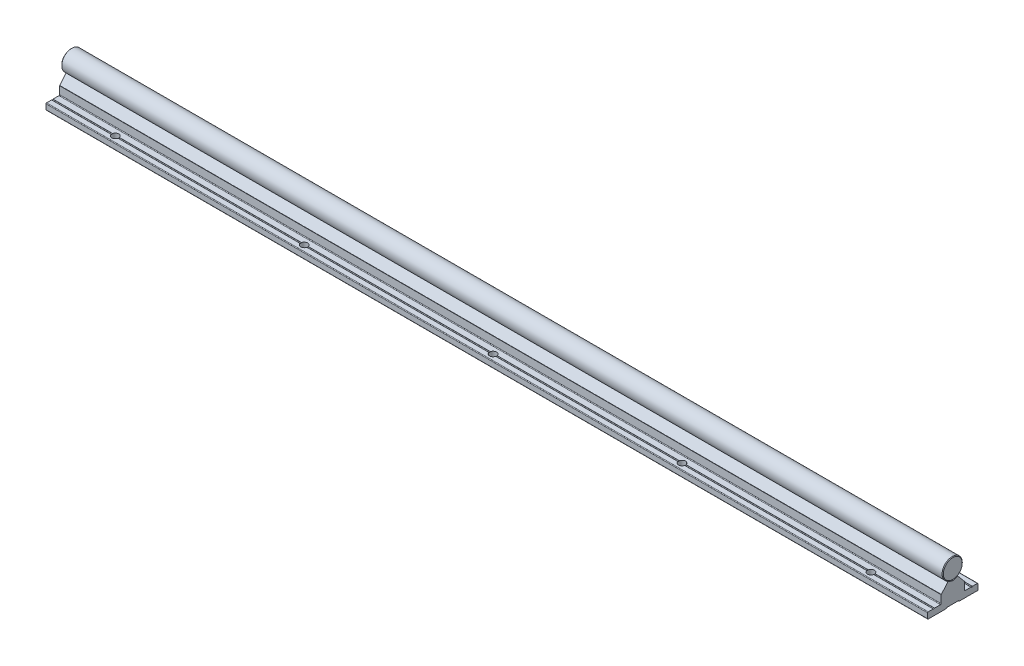
SolidWorks part; units mm, degrees
note: The reader was unsure of these and kept them because the rebuilt part matched: shared geometry of "Эскиз1<3>".
ref_plane "Спереди" through (0, 0, 0) normal (0, 0, 1) x (1, 0, 0)
ref_plane "Сверху" through (0, 0, 0) normal (0, 1, 0) x (1, 0, 0)
ref_plane "Справа" through (0, 0, 0) normal (1, 0, 0) x (0, 0, -1)
sketch "Эскиз1" plane through (0, 0, 0) normal (1, 0, 0) x (0, 0, -1)
  line L0 (0, 0) -> (0, -25) construction
  line L1 (0, -25) -> (-20, -25) construction
  line L2 (-4.75, -25) -> (-20, -25)
  line L3 (-20, -25) -> (-20, -20)
  line L4 (-20, -20) -> (-9.25, -20)
  line L5 (-9.25, -20) -> (-9.25, -13.3)
  line L6 (-9.25, -13.3) -> (-9.1101, -13.3)
  line L7 (-9.1101, -13.3) -> (-4, -7.21)
  line L8 (-4, -7.21) -> (-3.8, -7.21)
  line L9 (-3.8, -7.21) -> (0, -8.3557)
  line L10 (-2.75, -7.5266) -> (-2.75, -19) construction
  line L11 (-2.75, -19) -> (-4.75, -19) construction
  line L12 (-4.75, -19) -> (-4.75, -25) construction
  line L13 (-4.75, -25) -> (-4.75, -24.4)
  line L14 (-4.75, -24.4) -> (4.75, -24.4)
  line L15 (4.75, -25) -> (4.75, -24.4)
  line L16 (4.75, -25) -> (20, -25)
  line L17 (20, -25) -> (20, -20)
  line L18 (20, -20) -> (9.25, -20)
  line L19 (9.25, -20) -> (9.25, -13.3)
  line L20 (9.25, -13.3) -> (9.1101, -13.3)
  line L21 (9.1101, -13.3) -> (4, -7.21)
  line L22 (4, -7.21) -> (3.8, -7.21)
  line L23 (3.8, -7.21) -> (0, -8.3557)
  line L24 (-15, -20) -> (-15, -25) construction
  line L25 (-15.5, -20) -> (-15, -20.5)
  line L26 (-15, -20.5) -> (-14.5, -20)
  line L27 (15.5, -20) -> (15, -20.5)
  line L28 (15, -20) -> (15, -25) construction
  line L29 (15, -20.5) -> (14.5, -20)
  circle A0 centre (0, 0) radius 8
  point P17 (0, -24.4)
  dimension "D1" = 16
  dimension "D2" = 17.79
  dimension "D3" = 8
  dimension "D4" = 40
  dimension "D5" = 0.2
  dimension "D6" = 18.5
  dimension "D7" = 5
  dimension "D8" = 40
  dimension "D9" = 11.7
  dimension "D10" = 4.75
  dimension "D11" = 2.75
  dimension "D12" = 6
  dimension "D13" = 0.6
  dimension "D14" = 1
  dimension "D15" = 15
  dimension "D16" = 25
extrude "Опора" add sketch "Эскиз1" along normal mid plane 700 contours L27 L29 L18 L19 L20 L21 L22 L23 L9 L8 L7 L6 L5 L4 L26 L25 L3 L2 L13 L14 L15 L16 L17
extrude "Вал" add sketch "Эскиз1<3>" along normal mid plane 700 separate body contours A0
sketch "Эскиз1<3>" plane through (0, 0, 0) normal (1, 0, 0) x (0, 0, -1) same geometry as "Эскиз1"
fillet "Скругление4" radius 0.2 7 edges at (0, -20, -15.5) (0, -20, -14.5) (0, -20, 14.5) (0, -20, 15.5) (0, -8.3557, 0) (0, -24.4, -4.75) (0, -24.4, 4.75)
sketch "Эскиз2" plane through (0, -20, 0) normal (0, 1, 0) x (1, 0, 0)
  line L0 (-300, 15) -> (-300, -15) construction
  line L1 (350, 15) -> (-350, 15) construction
  line L2 (350, -15) -> (-350, -15) construction
  line L3 (-350, 8) -> (-350, -8) construction
  line L4 (-150, 15) -> (-150, -15) construction
  line L5 (0, 15) -> (0, -15) construction
  line L6 (150, 15) -> (150, -15) construction
  line L7 (300, 15) -> (300, -15) construction
  line L8 (450, 15) -> (450, -15) construction
  line L9 (600, 15) -> (600, -15) construction
  line L10 (750, 15) -> (750, -15) construction
  line L11 (900, 15) -> (900, -15) construction
  line L12 (1050, 15) -> (1050, -15) construction
  line L13 (1200, 15) -> (1200, -15) construction
  line L14 (1350, 15) -> (1350, -15) construction
  line L15 (1500, 15) -> (1500, -15) construction
  line L16 (1650, 15) -> (1650, -15) construction
  line L17 (1800, 15) -> (1800, -15) construction
  line L18 (1950, 15) -> (1950, -15) construction
  line L19 (2100, 15) -> (2100, -15) construction
  line L20 (2250, 15) -> (2250, -15) construction
  line L21 (2400, 15) -> (2400, -15) construction
  line L22 (2550, 15) -> (2550, -15) construction
  circle A0 centre (-300, -15) radius 2.75
  circle A1 centre (-300, 15) radius 2.75
  circle A2 centre (-150, -15) radius 2.75
  circle A3 centre (-150, 15) radius 2.75
  circle A4 centre (0, -15) radius 2.75
  circle A5 centre (0, 15) radius 2.75
  circle A6 centre (150, -15) radius 2.75
  circle A7 centre (150, 15) radius 2.75
  circle A8 centre (300, -15) radius 2.75
  circle A9 centre (300, 15) radius 2.75
  circle A10 centre (450, -15) radius 2.75
  circle A11 centre (450, 15) radius 2.75
  circle A12 centre (600, -15) radius 2.75
  circle A13 centre (600, 15) radius 2.75
  circle A14 centre (750, -15) radius 2.75
  circle A15 centre (750, 15) radius 2.75
  circle A16 centre (900, -15) radius 2.75
  circle A17 centre (900, 15) radius 2.75
  circle A18 centre (1050, -15) radius 2.75
  circle A19 centre (1050, 15) radius 2.75
  circle A20 centre (1200, -15) radius 2.75
  circle A21 centre (1200, 15) radius 2.75
  circle A22 centre (1350, -15) radius 2.75
  circle A23 centre (1350, 15) radius 2.75
  circle A24 centre (1500, -15) radius 2.75
  circle A25 centre (1500, 15) radius 2.75
  circle A26 centre (1650, -15) radius 2.75
  circle A27 centre (1650, 15) radius 2.75
  circle A28 centre (1800, -15) radius 2.75
  circle A29 centre (1800, 15) radius 2.75
  circle A30 centre (1950, -15) radius 2.75
  circle A31 centre (1950, 15) radius 2.75
  circle A32 centre (2100, -15) radius 2.75
  circle A33 centre (2100, 15) radius 2.75
  circle A34 centre (2250, -15) radius 2.75
  circle A35 centre (2250, 15) radius 2.75
  circle A36 centre (2400, -15) radius 2.75
  circle A37 centre (2400, 15) radius 2.75
  circle A38 centre (2550, -15) radius 2.75
  circle A39 centre (2550, 15) radius 2.75
  dimension "D1" = 5.5
  dimension "D2" = 5.5
  dimension "D6" = 5.5
  dimension "D7" = 5.5
  dimension "D3" = 50
  dimension "D5" = 150
  dimension "D4" = 20
extrude "Вырез-Вытянуть1" cut sketch "Эскиз2" against normal through all
sketch "Эскиз3" plane through (0, 0, 0) normal (0, 0, 1) x (1, 0, 0)
  line L0 (-300, 56.4349) -> (-300, -59.6123) construction
  line L1 (-350, 8) -> (-350, -8) construction
  line L2 (-350, 0) -> (-300, 0) construction
  line L3 (-300, 0) -> (-302.2, -1.2702)
  line L4 (-302.2, -1.2702) -> (-302.2, -7.5)
  line L5 (-302.2, -7.5) -> (-302.75, -7.5)
  line L6 (-302.75, -7.5) -> (-302.75, -19)
  line L7 (-302.75, -19) -> (-304.75, -19)
  line L8 (-304.75, -19) -> (-304.75, -24.4)
  line L10 (-304.75, -24.4) -> (-300, -24.4)
  line L11 (-300, -24.4) -> (-300, 0)
  line L13 (350, -25) -> (-350, -25) construction
  line L14 (-350, -24.4) -> (350, -24.4) construction
  dimension "D1" = 50
  dimension "D2" = 9.5
  dimension "D3" = 60
  dimension "D5" = 2.75
  dimension "D7" = 4.4
  dimension "D6" = 7.5
  dimension "D4" = 6
revolve "Вырез-Повернуть1" cut sketch "Эскиз3" angle 360 about L0
pattern_linear "Линейный массив1" count 5 spacing 150 along (1, 0, 0) of "Вырез-Повернуть1"
sketch "Эскиз4" plane through (0, 0, 0) normal (0, 0, 1) x (1, 0, 0)
  line L0 (-300, 39.8402) -> (-300, -50.2749) construction
  line L1 (-350, 8) -> (-350, -8) construction
  line L2 (-350, 0) -> (-300, 0) construction
  line L3 (-300, -10) -> (-302.2, -10)
  line L4 (-302.2, -10) -> (-302.2, -1.2702)
  line L5 (-302.2, -1.2702) -> (-300, 0)
  line L6 (-300, 0) -> (-300, -10)
  dimension "D1" = 50
  dimension "D2" = 60
  dimension "D3" = 2.2
  dimension "D4" = 10
revolve "Вырез-Повернуть2" cut sketch "Эскиз4" angle 360 about L0
pattern_linear "Линейный массив2" count 5 spacing 150 along (1, 0, 0) of "Вырез-Повернуть2"
sketch "Эскиз5" plane through (0, 0, 0) normal (0, 0, 1) x (1, 0, 0)
  line L0 (-300, 35.5296) -> (-300, -41.3293) construction
  line L1 (-350, 8) -> (-350, -8) construction
  line L2 (-300, -24) -> (-304.5, -24)
  line L3 (-304.5, -24) -> (-304.5, -19)
  line L4 (-304.75, -19) -> (-295.25, -19) construction
  line L5 (-304.5, -19) -> (-302.5, -19)
  line L6 (-302.5, -19) -> (-302.5, -2.4619)
  line L7 (-302.5, -2.4619) -> (-301.7, -2)
  line L8 (-301.7, -2) -> (-300, -2)
  line L9 (-300, -2) -> (-300, -24)
  dimension "D1" = 50
  dimension "D2" = 0.8
  dimension "D3" = 30
  dimension "D4" = 5
  dimension "D5" = 17
  dimension "D7" = 9
revolve "Повернуть1" add sketch "Эскиз5" angle 360 about L0
fillet "Скругление1" radius 0.3 1 edges at (-300, -19, 4.5)
sketch "Эскиз6" plane through (0, -24, 0) normal (0, -1, 0) x (1, 0, 0)
  line L1 (-298.25, -1.0104) -> (-298.25, 1.0104)
  line L2 (-298.25, 1.0104) -> (-300, 2.0207)
  line L3 (-300, 2.0207) -> (-301.75, 1.0104)
  line L4 (-301.75, 1.0104) -> (-301.75, -1.0104)
  line L5 (-301.75, -1.0104) -> (-300, -2.0207)
  line L6 (-300, -2.0207) -> (-298.25, -1.0104)
  circle A0 centre (-300, 0) radius 1.75 construction
  dimension "D1" = 3.5
extrude "Вырез-Вытянуть2" cut sketch "Эскиз6" against normal blind 3
fillet "Скругление2" radius 0.3 7 edges at (-300, -24, 4.5) (-298.25, -24, 0) (-299.125, -24, 1.5155) (-300.875, -24, 1.5155) (-301.75, -24, 0) (-300.875, -24, -1.5155) (-299.125, -24, -1.5155)
pattern_linear "Линейный массив3" count 5 spacing 150 along (1, 0, 0) of bodies 114
chamfer "Фаска1" distance 0.5 angle 45 2 edges at (350, 0, -8) (-350, 0, -8)
fillet "Скругление3" radius 0.5 8 edges at (0, -20, -9.25) (0, -20, -20) (0, -25, -20) (0, -25, -4.75) (0, -25, 4.75) (0, -20, 9.25) (0, -25, 20) (0, -20, 20)
fillet "Скругление5" radius 0.2 4 edges at (0, -7.21, -3.8) (0, -7.21, -4) (0, -7.21, 4) (0, -7.21, 3.8)
fillet "Скругление6" radius 0.1 2 edges at (0, -13.3, -9.25) (0, -13.3, 9.25)
fillet "Скругление7" radius 0.1 2 edges at (0, -13.3, 9.1101) (0, -13.3, -9.1101)
equation "\"D1@Эскиз5\" = 50"
equation "\"D1@Эскиз3\"= \"D1@Эскиз5\""
equation "\"D1@Эскиз4\"= \"D1@Эскиз5\""
equation "\"D3@Эскиз2\"= \"D1@Эскиз5\""
